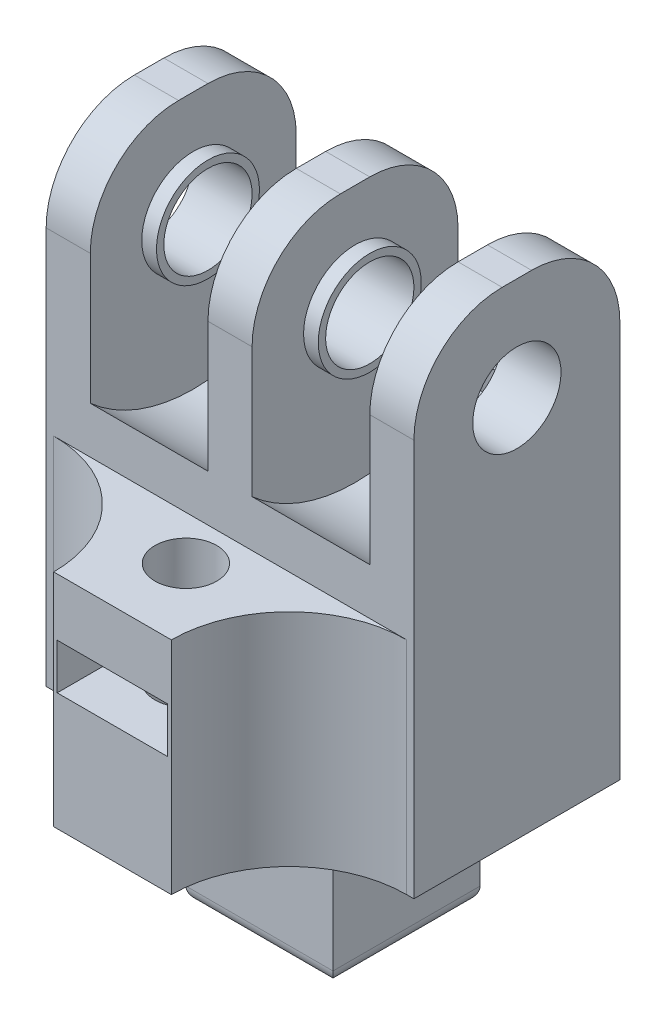
SolidWorks part; units mm, degrees
other "标注1"
sketch "草图2" plane through (25, 20, -5) normal (0.6833, 0.6393, -0.3527) x (-0.6957, 0.4235, -0.5802)
other "标注2"
sketch "草图14" plane through (0, 18, 7) normal (-0.1524, 0.0878, 0.9844) x (0.9837, 0.1098, 0.1425)
other "标注3"
sketch "草图19" plane through (0, -20, -15) normal (0, -1, 0) x (-1, 0, 0)
other "标注4"
sketch "草图21" plane through (0, -25, 15) normal (-0.1142, -0.0738, 0.9907) x (0.409, -0.9123, -0.0208)
ref_plane "前视基准面" through (0, 0, 0) normal (0, 0, 1) x (1, 0, 0)
ref_plane "上视基准面" through (0, 0, 0) normal (0, 1, 0) x (1, 0, 0)
ref_plane "右视基准面" through (0, 0, 0) normal (1, 0, 0) x (0, 0, -1)
sketch "草图1" plane through (0, 0, 0) normal (0, 0, 1) x (1, 0, 0)
  line L0 (-146.251, 0) -> (7166.2968, 0) construction
  line L5 (0, -146.251) -> (0, 7166.2968) construction
  line L6 (3, 0) -> (11, 0) construction
  line L7 (0, 0) -> (3, 0)
  line L8 (0, 0) -> (0, 18)
  line L9 (0, 18) -> (3, 18)
  line L10 (3, 0) -> (3, 18)
  line L11 (11, 0) -> (14, 0) construction
  line L12 (14, 0) -> (22, 0) construction
  line L13 (22, 0) -> (25, 0) construction
  line L14 (0, 0) -> (0, 11) construction
  line L15 (11, 0) -> (14, 0)
  line L16 (11, 0) -> (11, 18)
  line L17 (11, 18) -> (14, 18)
  line L18 (14, 0) -> (14, 18)
  line L19 (22, 0) -> (25, 0)
  line L20 (22, 0) -> (22, 18)
  line L21 (22, 18) -> (25, 18)
  line L22 (25, 0) -> (25, 18)
  line L23 (-1000, 11) -> (49000, 11) construction
  line L25 (0, 0) -> (25, 0)
  line L26 (0, 0) -> (0, -15)
  line L27 (0, -15) -> (25, -15)
  line L28 (25, 0) -> (25, -15)
  dimension "D1" = 3
  dimension "D2" = 18
  dimension "D3" = 11
  dimension "D4" = 8
  dimension "D5" = 8
  dimension "D6" = 15
  dimension "D7" = 18
ref_axis "基准轴2" through (-1000, 11, 0) along (1, 0, 0)
extrude "凸台-拉伸2" add sketch "草图1" along normal mid plane 14 contours L28 L19 L25 L15 L7 L26 L27 | L15 L18 L17 L16 | L19 L22 L21 L20 | L7 L10 L9 L8 region at (1.5, 9, 0) region at (12.5, -7.5, 0) region at (12.5, 9, 0) region at (23.5, 9, 0)
sketch "草图3" plane through (25, 0, 0) normal (1, 0, 0) x (0, 0, -1)
  circle A0 centre (0, 11) radius 3
extrude "切除-拉伸1" cut sketch "草图3" against normal through all and the other way through all from surface starting at face at (0, 1.5, 0)
sketch "草图15" plane through (3, 0, 0) normal (1, 0, 0) x (0, 0, -1)
  circle A0 centre (0, 11) radius 3
  circle A1 centre (0, 11) radius 3.5
  dimension "D1" = 0.5
extrude "凸台-拉伸11" add sketch "草图15" along normal blind 1
sketch "草图5" plane through (11, 0, 0) normal (-1, 0, 0) x (0, 0, 1)
  circle A0 centre (0, 11) radius 3
  circle A2 centre (0, 11) radius 3.5
  dimension "D1" = 0.5
extrude "凸台-拉伸6" add sketch "草图5" along normal blind 1 contours A2 | A0
sketch "草图6" plane through (14, 0, 0) normal (1, 0, 0) x (0, 0, -1)
  circle A0 centre (0, 11) radius 3
  circle A2 centre (0, 11) radius 3
  circle A3 centre (0, 11) radius 3.5
  circle M2 centre (0, 11) radius 3
  dimension "D1" = 0.5
extrude "凸台-拉伸7" add sketch "草图6" along normal blind 1 contours A3 M2 region at (14, 11, 3.401)
sketch "草图7" plane through (22, 0, 0) normal (-1, 0, 0) x (0, 0, 1)
  circle A0 centre (0, 11) radius 3
  circle A2 centre (0, 11) radius 3.5
  dimension "D1" = 0.5
extrude "凸台-拉伸8" add sketch "草图7" along normal blind 1
fillet "圆角1" radius 6 6 edges at (23.5, 18, -7) (23.5, 18, 7) (12.5, 18, 7) (1.5, 18, 7) (1.5, 18, -7) (12.5, 18, -7)
sketch "草图8" plane through (0, -15, 0) normal (0, -1, 0) x (1, 0, 0)
  line L0 (12.5, -993) -> (12.5, 49007) construction
  line L1 (0, 7) -> (25, 7)
  line L2 (0, 7) -> (0, -7)
  line L3 (0, -7) -> (25, -7)
  line L4 (25, 7) -> (25, -7)
  line L5 (11, 0) -> (14, 0) construction
  line L6 (7.5, -5) -> (17.5, -5)
  line L7 (7.5, -5) -> (7.5, 5)
  line L8 (7.5, 5) -> (17.5, 5)
  line L9 (17.5, -5) -> (17.5, 5)
  line L10 (7.5, -5) -> (17.5, 5) construction
  line L11 (7.5, 5) -> (17.5, -5) construction
  point P7 (12.5, 0)
  point P9 (12.5, 7)
  dimension "D1" = 25
  dimension "D2" = 14
  dimension "D3" = 10
  dimension "D4" = 10
extrude "凸台-拉伸9" add sketch "草图8" along normal blind 10 contours L7 L6 L9 L8
fillet "圆角2" radius 1 4 edges at (17.5, -25, 0) (12.5, -25, -5) (7.5, -25, 0) (12.5, -25, 5)
ref_plane "基准面1" through (0, -7, 0) normal (0, -1, 0) x (-1, 0, 0)
sketch "草图23" plane through (0, 0, 0) normal (-1, 0, 0) x (0, 0, 1)
  line L0 (7, -15) -> (7, -7)
  line L1 (-7.7, -7) -> (7.7, -7) construction
  line L2 (7, 12) -> (7, -15) construction
  line L3 (7, -7) -> (-7, -7)
  line L4 (-7, 12) -> (-7, -15) construction
  line L5 (-7, -7) -> (-7, 7.3703)
  line L6 (7, -7) -> (7, 7.8252)
  circle A0 centre (0, 11) radius 10.5
  line M4 (7, -15) -> (7, 12)
  dimension "D1" = 21
extrude "凸台-拉伸14" add sketch "草图23" against normal up to surface (22 mm away) contours A0 L5 L3 M4 region at (0, -2.7935, 0) up to face at (22, 10.4142, 0)
sketch "草图17" plane through (0, -7, 0) normal (0, -1, 0) x (-1, 0, 0)
  line L0 (-12.5, -993) -> (-12.5, 49007) construction
  line L1 (0, 7) -> (-25, 7) construction
  line L2 (-12.5, 7) -> (-12.5, 10) construction
  line L3 (-12.5, 7) -> (-8.5125, 7) construction
  line L4 (-8.5125, 7) -> (-8.5125, 15) construction
  line L6 (-8.5125, 15) -> (-16.5125, 15)
  line L7 (-8.5125, 15) -> (-8.5125, 7)
  line L8 (-8.5125, 7) -> (-16.5125, 7)
  line L9 (-16.5125, 15) -> (-16.5125, 7)
  circle A0 centre (-12.5, 10) radius 2.1
  point P5 (-12.5, 7)
  dimension "D1" = 8
  dimension "D2" = 8
extrude "凸台-拉伸12" add sketch "草图17" along normal up to surface (8 mm away) up to face at (12.5, -15, 0)
sketch "草图18" plane through (0, -7, 0) normal (0, -1, 0) x (-1, 0, 0)
  line L0 (-16.25, 12.1651) -> (-16.25, 15)
  line L1 (-12.5, 14.3301) -> (-16.25, 12.1651)
  line L2 (-16.25, 12.1651) -> (-16.25, 7.8349)
  line L3 (-16.25, 7.8349) -> (-12.5, 5.6699)
  line L4 (-12.5, 5.6699) -> (-8.75, 7.8349)
  line L5 (-8.75, 7.8349) -> (-8.75, 12.1651)
  line L6 (-8.75, 12.1651) -> (-12.5, 14.3301)
  line L7 (-16.5125, 15) -> (-8.5125, 15) construction
  line L8 (-16.25, 15) -> (-8.75, 15)
  line L9 (-8.75, 15) -> (-8.75, 12.1651)
  circle A0 centre (-12.5, 10) radius 3.75 construction
  dimension "D1" = 7.5
extrude "凸台-拉伸13" add sketch "草图17<2>" against normal blind 7
sketch "草图17<2>" plane through (0, -7, 0) normal (0, -1, 0) x (-1, 0, 0) same geometry as "草图17"
extrude "切除-拉伸2" cut sketch "草图18" against normal blind 3.1 contours L9 L8 L0 L1 L6 | L5 L6 L1 L2 L3 L4 region at (16.1698, -7, -13.5825) region at (12.5, -7, -10)
mirror "镜向1" about plane through (0, 0, 0) normal (0, 0, 1) of "凸台-拉伸12", "凸台-拉伸13", "切除-拉伸2"
fillet "圆角4" radius 8 4 edges at (8.5125, -7.5, -7) (16.5125, -7.5, -7) (16.5125, -7.5, 7) (8.5125, -7.5, 7)
